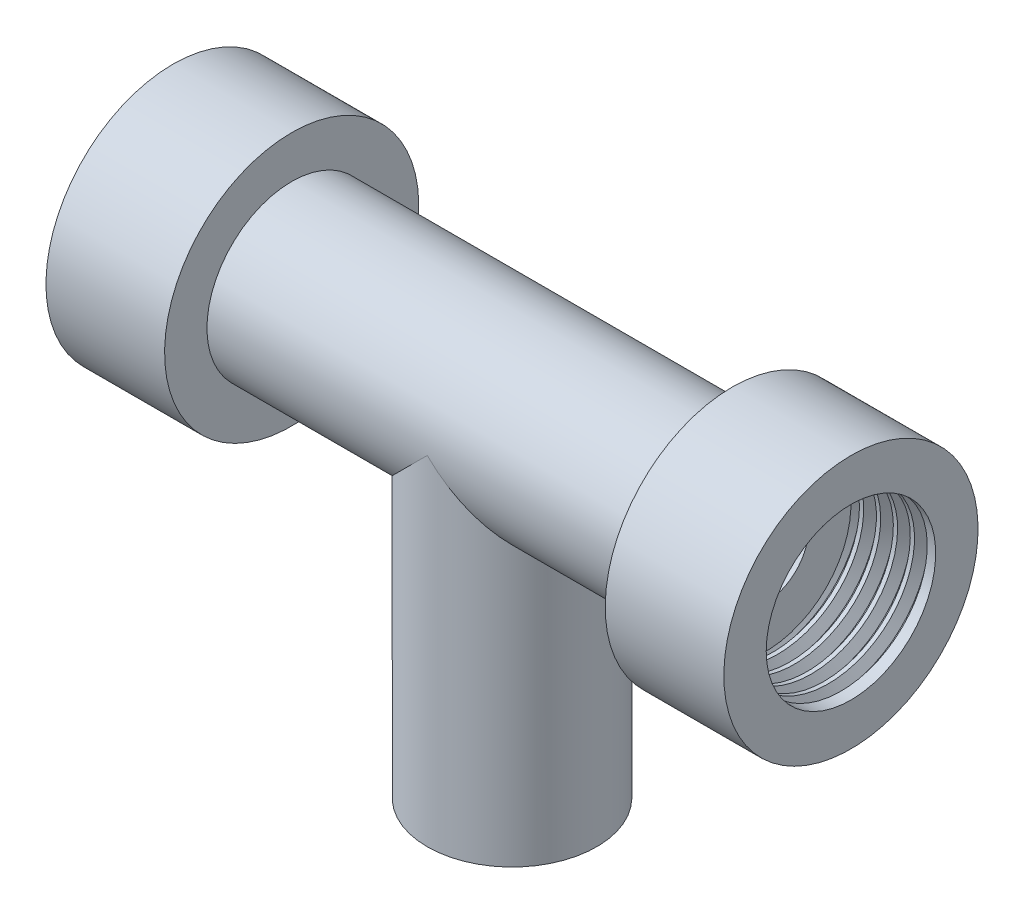
SolidWorks part; units mm, degrees
ref_plane "Front Plane" through (0, 0, 0) normal (0, 0, 1) x (1, 0, 0)
ref_plane "Top Plane" through (0, 0, 0) normal (0, 1, 0) x (1, 0, 0)
ref_plane "Right Plane" through (0, 0, 0) normal (1, 0, 0) x (0, 0, -1)
sketch "Sketch1" plane through (0, 0, 0) normal (0, 0, 1) x (1, 0, 0)
  line L1 (0, 0) -> (6.35, 0)
  line L2 (0, 0) -> (0, -25.4)
  line L3 (0, -25.4) -> (6.35, -25.4)
  line L4 (6.35, 0) -> (6.35, -25.4)
  dimension "D1" = 25.4
  dimension "D2" = 6.35
revolve "Revolve1" add sketch "Sketch1" angle 360 about L2
sketch "Sketch2" plane through (0, 0, 0) normal (0, 0, 1) x (1, 0, 0)
  line L0 (0, 0) -> (0, -6.35)
  line L1 (0, -6.35) -> (16.51, -6.35)
  line L2 (16.51, -6.35) -> (16.51, -9.525)
  line L3 (16.51, -9.525) -> (25.4, -9.525)
  line L4 (25.4, -9.525) -> (25.4, -6.35)
  line L5 (25.4, -6.35) -> (19.05, -6.35)
  line L6 (19.05, -6.35) -> (19.05, 0)
  line L7 (19.05, 0) -> (0, 0)
  dimension "D1" = 6.35
  dimension "D2" = 19.05
  dimension "D3" = 16.51
  dimension "D4" = 6.35
  dimension "D5" = 3.175
revolve "Revolve2" add sketch "Sketch2" angle 360 about L7
mirror "Mirror1" about plane through (0, 0, 0) normal (1, 0, 0) of "Revolve2"
sketch "Sketch3" plane through (0, -25.4, 0) normal (0, -1, 0) x (1, 0, 0)
  circle A0 centre (0, 0) radius 3.175
  dimension "D1" = 6.35
extrude "Cut-Extrude1" cut sketch "Sketch3" against normal blind 25.4
sketch "Sketch4" plane through (-19.05, 0, 0) normal (-1, 0, 0) x (0, 0, 1)
  circle A0 centre (0, 0) radius 3.175
  dimension "D1" = 6.35
extrude "Cut-Extrude2" cut sketch "Sketch4" against normal blind 38.1
thread "Thread1" pitch 1.27 method cut profile "Thread Profile1" start angle 0, offset 0, length 0, pitch 1.27, diameter 12.7
ref_plane "Plane1" through (25.4, 0, 6.35) normal (0, -1, 0) x (0, 0, 1)
sketch "Thread Profile1" plane through (25.4, 0, 6.35) normal (0, -1, 0) x (0, 0, 1)
  line L0 (0, 0) -> (0, 1.27) construction
  line L1 (0, 0) -> (0.6874, 0.3969)
  line L2 (0.6874, 0.3969) -> (0.6874, 0.5556)
  line L3 (0.6874, 0.5556) -> (0, 0.9525)
  line L4 (0.6874, 0.4762) -> (0, 0.4762) construction
  line L11 (0, 0) -> (0, 0.9525)
  point P2 (0, 0)
  dimension "Pitch" = 1.27
  dimension "Profile_Angle" = 60
  dimension "Profile_Land" = 0.1588
  dimension "Profile_Height" = 0.6874
thread "Thread2" pitch 1.27 method cut profile "Thread Profile2" start angle 0, offset 0, length 0, pitch 1.27, diameter 12.7
ref_plane "Plane2" through (-25.4, 0, -6.35) normal (0, -1, 0) x (0, 0, -1)
sketch "Thread Profile2" plane through (-25.4, 0, -6.35) normal (0, -1, 0) x (0, 0, -1)
  line L0 (0, 0) -> (0, 1.27) construction
  line L1 (0, 0) -> (0.6874, 0.3969)
  line L2 (0.6874, 0.3969) -> (0.6874, 0.5556)
  line L3 (0.6874, 0.5556) -> (0, 0.9525)
  line L4 (0.6874, 0.4762) -> (0, 0.4762) construction
  line L11 (0, 0) -> (0, 0.9525)
  point P2 (0, 0)
  dimension "Pitch" = 1.27
  dimension "Profile_Angle" = 60
  dimension "Profile_Land" = 0.1588
  dimension "Profile_Height" = 0.6874
